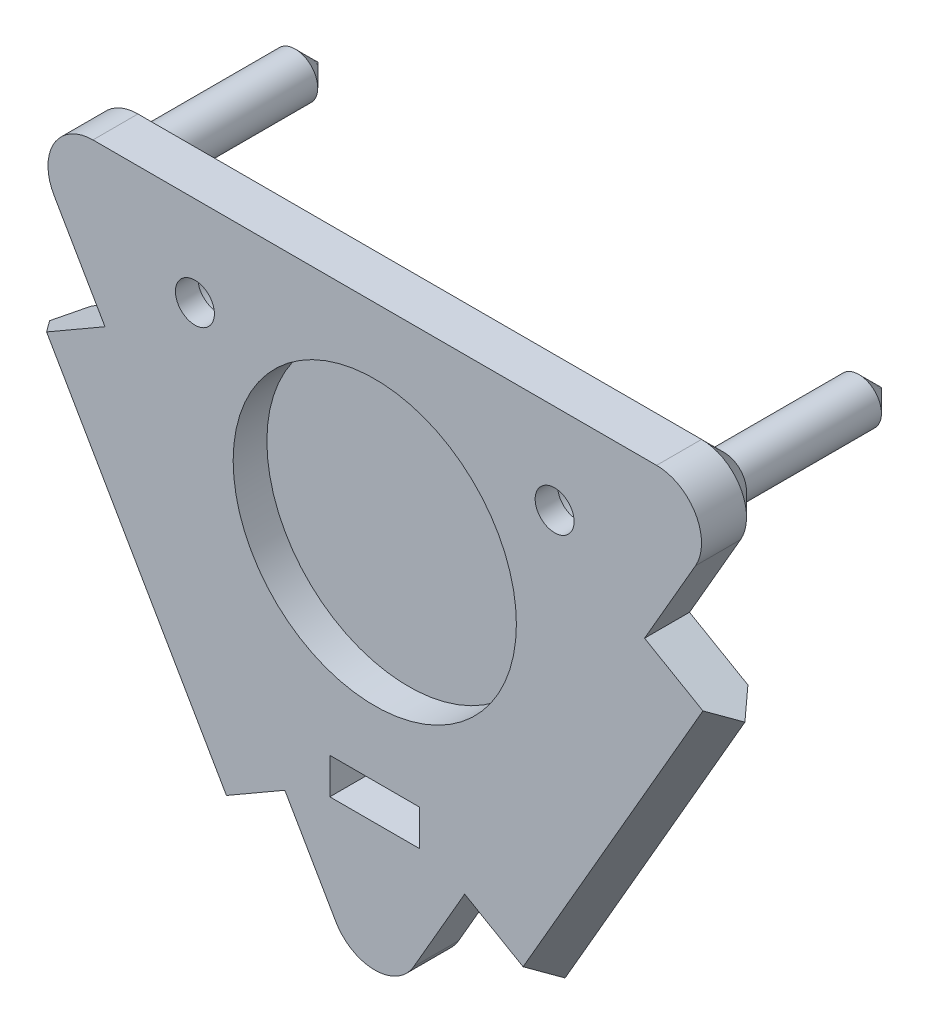
SolidWorks part; units mm, degrees
material "6061 Alloy"
ref_plane "Front" through (0, 0, 0) normal (0, 0, 1) x (1, 0, 0)
ref_plane "Top" through (0, 0, 0) normal (0, 1, 0) x (1, 0, 0)
ref_plane "Right" through (0, 0, 0) normal (1, 0, 0) x (0, 0, -1)
sketch "Sketch1" plane through (0, 0, 0) normal (0, 0, 1) x (1, 0, 0)
  line L0 (50.8, 29.3294) -> (0, -58.6588)
  line L1 (0, -58.6588) -> (-50.8, 29.3294)
  line L2 (-50.8, 29.3294) -> (50.8, 29.3294)
  line L3 (25.4, -14.6647) -> (0, 0) construction
  line L4 (0, 0) -> (-25.4, -14.6647) construction
  line L5 (0, 29.3294) -> (0, 0) construction
  point P6 (0, 0)
  point P8 (-48.5181, 32.9673)
  dimension "D1" = 101.6
extrude "Boss-Extrude1" add sketch "Sketch1" along normal mid plane 6.35
fillet "Fillet1" radius 6.35 3 edges at (-50.8, 29.3294, 0) (0, -58.6588, 0) (50.8, 29.3294, 0)
sketch "Sketch3" plane through (0, 0, 3.175) normal (0, 0, 1) x (1, 0, 0)
  circle A0 centre (0, 0) radius 20
  dimension "D1" = 40
extrude "Cut-Extrude1" cut sketch "Sketch3" against normal offset from surface (4.7625 mm away) 1.5875 up to face at (0, 0, -3.175)
sketch "Sketch8" plane through (0, 0, -3.175) normal (0, 0, -1) x (-1, 0, 0)
  circle A0 centre (0, -45.9588) radius 3.175
  arc A1 (-5.4993, -49.1338) -> (5.4993, -49.1338) centre (0, -45.9588) ccw construction
  dimension "D1" = 6.35
extrude "Boss-Extrude2" add sketch "Sketch8" along normal blind 25.4
chamfer "Chamfer1" distance 3.175 angle 45 1 edges at (-3.175, -45.9588, -3.175)
chamfer "Chamfer2" distance 3.175 angle 45 1 edges at (-3.175, -45.9588, -28.575)
ref_axis "Axis2" through (0, 0, -80.9) along (0, 0, 1)
pattern_circular "CirPattern2" count 3 over 360 about axis through (0, 0, -80.9) along (0, 0, 1) of "Chamfer1", "Boss-Extrude2", "Chamfer2"
sketch "Sketch9" plane through (0, 0, 3.175) normal (0, 0, 1) x (1, 0, 0)
  line L1 (-6.35, -34.29) -> (6.35, -34.29)
  line L2 (-6.35, -34.29) -> (-6.35, -29.21)
  line L3 (-6.35, -29.21) -> (6.35, -29.21)
  line L4 (6.35, -34.29) -> (6.35, -29.21)
  line L5 (-6.35, -34.29) -> (6.35, -29.21) construction
  line L6 (-6.35, -29.21) -> (6.35, -34.29) construction
  point P0 (0, -31.75)
  point P5 (0, 0)
  dimension "D1" = 5.08
  dimension "D2" = 12.7
  dimension "D3" = 31.75
extrude "Cut-Extrude4" cut sketch "Sketch9" against normal through all
sketch "Sketch10" plane through (0, 0, 3.175) normal (0, 0, 1) x (1, 0, 0)
  line L1 (0, 0) -> (-25.4, 16.6294) construction
  line L2 (-25.4, 16.6294) -> (25.4, 16.6294) construction
  line L3 (39.8015, 29.3294) -> (-39.8015, 29.3294) construction
  circle A0 centre (-25.4, 16.6294) radius 2.75
  circle A1 centre (25.4, 16.6294) radius 2.75
  point P6 (0, 16.6294)
  dimension "D1" = 5.5
  dimension "D2" = 12.7
  dimension "D3" = 50.8
extrude "Cut-Extrude5" cut sketch "Sketch10" against normal through all
sketch "Sketch11" plane through (0, 0, -3.175) normal (0, 0, -1) x (-1, 0, 0)
  circle A0 centre (-25.4, 16.6294) radius 5
  circle A2 centre (25.4, 16.6294) radius 5
  circle A3 centre (-25.4, 16.6294) radius 2.75 construction
  point P2 (0, 0)
  dimension "D1" = 10
extrude "Cut-Extrude6" cut sketch "Sketch11" against normal blind 3.175
sketch "Sketch12" plane through (0, 0, 3.175) normal (0, 0, 1) x (1, 0, 0)
  line L0 (-49.0985, 0.9823) -> (-23.6985, -43.0117)
  line L1 (-49.0985, 0.9823) -> (-38.1, 7.3323)
  line L2 (-23.6985, -43.0117) -> (-12.7, -36.6617)
  line L3 (-38.1, 7.3323) -> (-12.7, -36.6617)
  line L4 (-49.0985, 0.9823) -> (-12.7, -36.6617) construction
  line L5 (-23.6985, -43.0117) -> (-38.1, 7.3323) construction
  line L6 (-45.3007, 19.8044) -> (-5.4993, -49.1338) construction
  point P1 (-30.8993, -17.8397)
  point P3 (-25.4, -14.6647)
  point P8 (-25.4, -14.6647)
  dimension "D1" = 50.8
  dimension "D2" = 12.7
extrude "Boss-Extrude3" add sketch "Sketch12" against normal up to surface (6.35 mm away) up to face at (20.4, 16.6294, -3.175)
chamfer "Chamfer3" distance 3.175 angle 45 2 edges at (-36.3985, -21.0147, -3.175) (-36.3985, -21.0147, 3.175)
mirror "Mirror2" about plane through (0, 0, 0) normal (1, 0, 0) of "Chamfer3", "Boss-Extrude3"
